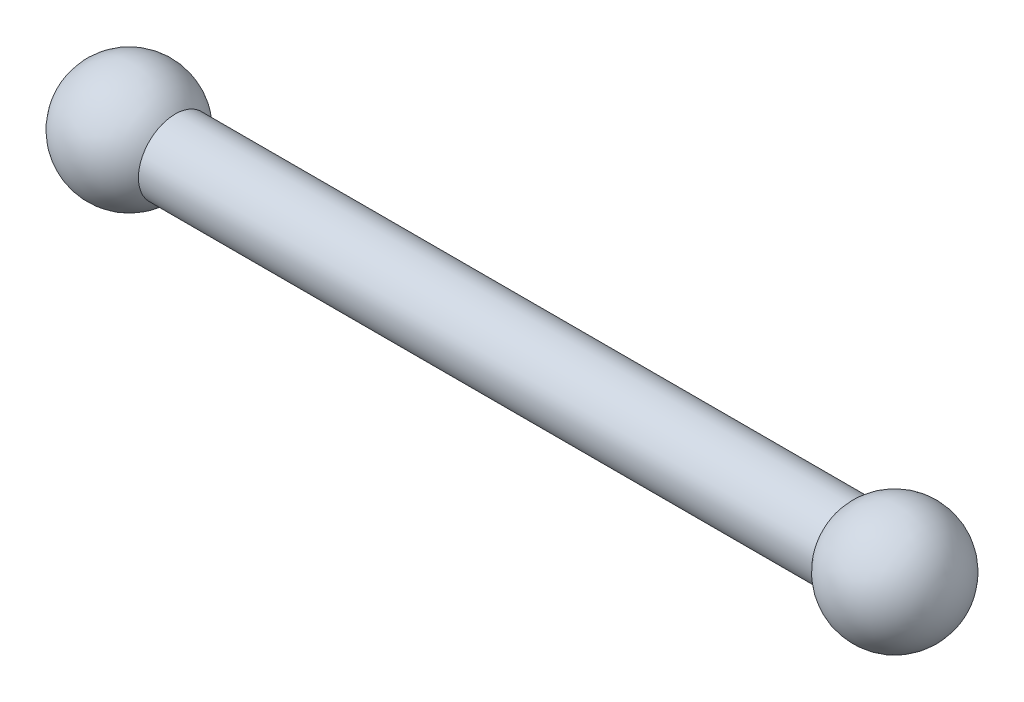
SolidWorks part; units mm, degrees
material "1060 Alloy"
ref_plane "Front Plane" through (0, 0, 0) normal (0, 0, 1) x (1, 0, 0)
ref_plane "Top Plane" through (0, 0, 0) normal (0, 1, 0) x (1, 0, 0)
ref_plane "Right Plane" through (0, 0, 0) normal (1, 0, 0) x (0, 0, -1)
sketch "Sketch1" plane through (0, 0, 0) normal (0, 0, 1) x (1, 0, 0)
  line L0 (0, 0) -> (0, 103.0383) construction
  line L1 (0, 0) -> (0, 12.7)
  line L2 (0, 12.7) -> (116.2177, 12.7)
  line L3 (0, 0) -> (152.4, 0)
  line L4 (0, 0) -> (399.4988, 0) construction
  arc A2 (116.2177, 12.7) -> (152.4, 0) centre (132.08, 0) cw
  dimension "D3" = 20.32
  dimension "D1" = 12.7
  dimension "D2" = 152.4
revolve "Revolve1" add sketch "Sketch1" angle 360 about L4
mirror "Mirror1" about plane through (0, 0, 0) normal (1, 0, 0) of "Revolve1"
sketch "Sketch2" plane through (0, 0, 0) normal (0, 0, 1) x (1, 0, 0)
  line L0 (0, 0) -> (0, 57.9452) construction
  point P3 (0, 57.9452)
ref_axis "Axis1" through (0, 0, 0) along (0, 1, 0)
